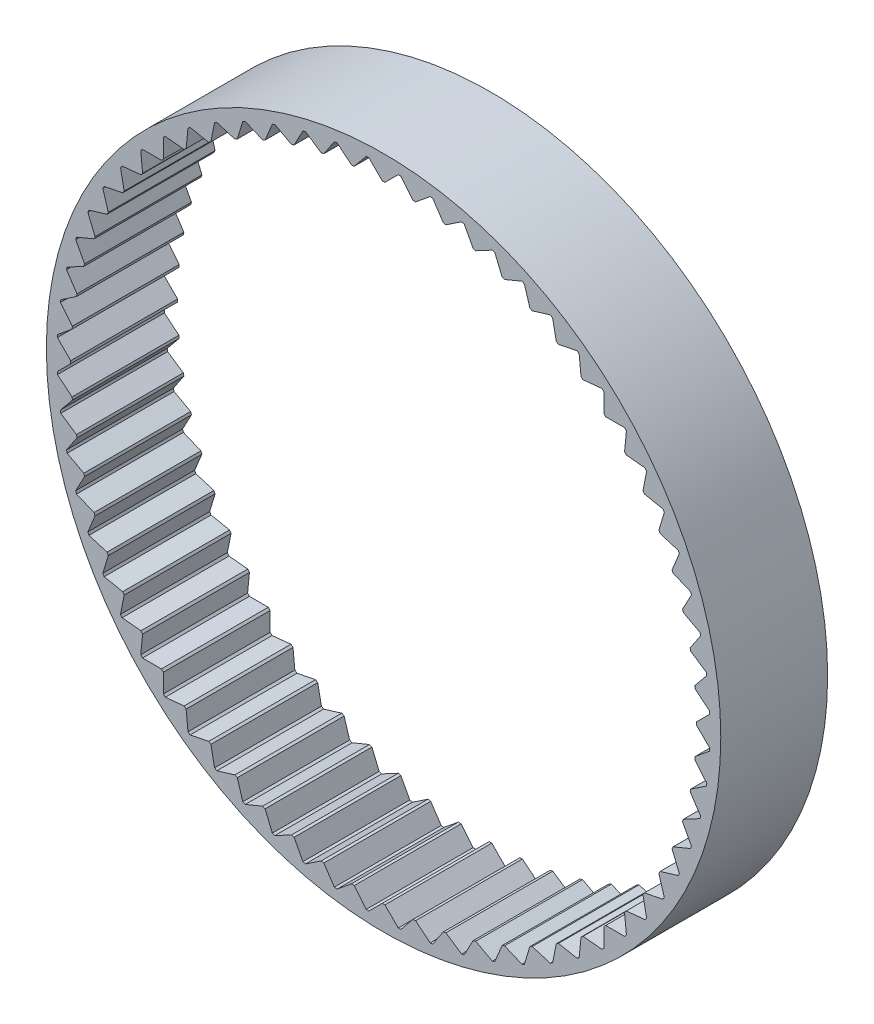
SolidWorks part; units mm, degrees
ref_plane "Front Plane" through (0, 0, 0) normal (0, 0, 1) x (1, 0, 0)
ref_plane "Top Plane" through (0, 0, 0) normal (0, 1, 0) x (1, 0, 0)
ref_plane "Right Plane" through (0, 0, 0) normal (1, 0, 0) x (0, 0, -1)
sketch "Sketch1" plane through (0, 0, 0) normal (0, 0, 1) x (1, 0, 0)
  circle A0 centre (0, 0) radius 61.1155
  circle A1 centre (0, 0) radius 63.1155
  dimension "D1" = 122.231
  dimension "D2" = 2
extrude "Boss-Extrude1" add sketch "Sketch1" along normal blind 20
sketch "Sketch2" plane through (0, 0, 0) normal (0, 0, -1) x (-1, 0, 0)
  line L0 (-2.7491, 61.0536) -> (-0.2491, 58.5536)
  line L1 (-0.2491, 58.5536) -> (0.2491, 58.5536)
  line L2 (0.2491, 58.5536) -> (2.7491, 61.0536)
  line L3 (-2.7491, 61.0536) -> (2.7491, 61.0536) construction
  circle A0 centre (0, 0) radius 61.1155 construction
  arc A1 (-2.7491, 61.0536) -> (2.7491, 61.0536) centre (0, 0) cw
  point P7 (0, 61.0536)
  point P9 (0, 58.5536)
  dimension "D1" = 45
  dimension "D3" = 2.5
  dimension "D2" = 5.5
extrude "Boss-Extrude2" add sketch "Sketch2" against normal up to surface (20 mm away) up to face at (63.1155, 0, 20)
pattern_circular "CirPattern1" count 64 over 360 about axis through (0, 0, 0) along (0, 0, 1) of "Boss-Extrude2"
equation "\"hb\"= 4.5mm"
equation "\"ht\"= 2.5mm"
equation "\"pitch\"= 6mm"
equation "\"bt\"= 5.5mm"
equation "\"tooth_angle\"= 45deg"
equation "\"circumference\"= \"pitch\" * \"num_teeth\""
equation "\"diameter\"= \"circumference\" / pi"
equation "\"D1@Sketch1\"=\"diameter\""
equation "\"D2@Sketch1\"= \"hb\" - \"ht\""
equation "\"width\"= 20mm"
equation "\"D1@Boss-Extrude1\"= \"width\""
equation "\"D2@Sketch2\"= \"bt\""
equation "\"D1@Sketch2\"=\"tooth_angle\""
equation "\"D3@Sketch2\"=\"ht\""
equation "\"num_teeth\"= 64"
equation "\"D1@CirPattern1\"=\"num_teeth\""
equation "\"D2@CirPattern1\"= 360 / \"num_teeth\""
equation "\"D2@Sketch4\"= \"hb\""
equation "\"endcap_thickness\"= 0.4mm"
equation "\"D19@Boss-Extrude6\"= \"endcap_thickness\""
equation "\"D1@Boss-Extrude6\"= \"endcap_thickness\""
equation "\"D1@Boss-Extrude7\"=\"endcap_thickness\""
